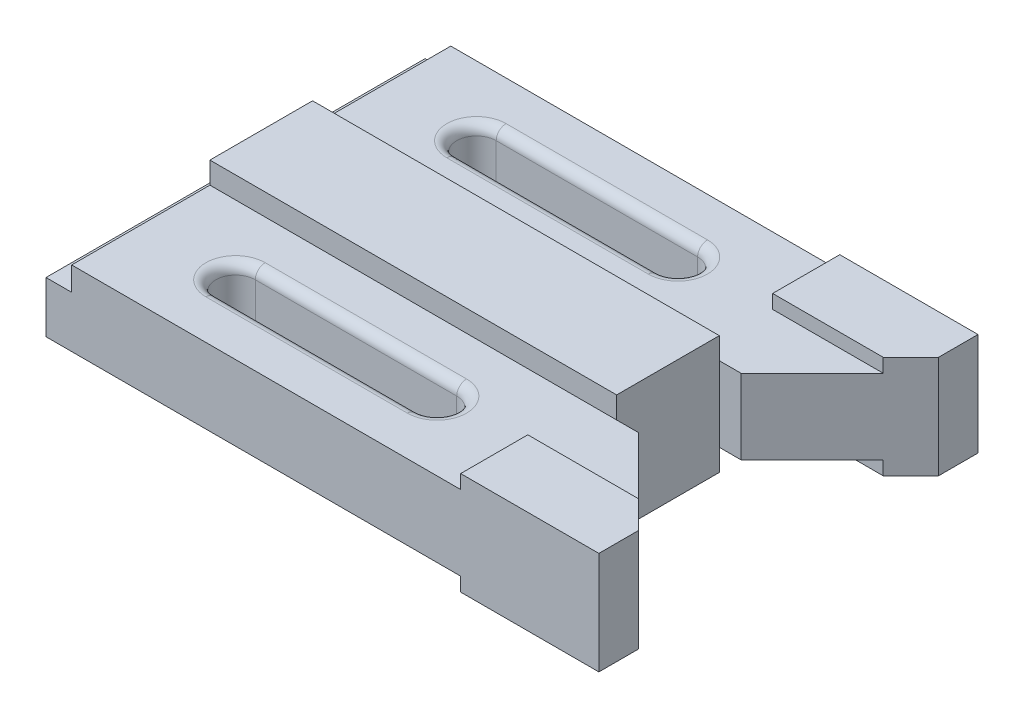
SolidWorks part; units mm, degrees
material "1060 Alloy"
ref_plane "Front Plane" through (0, 0, 0) normal (0, 0, 1) x (1, 0, 0)
ref_plane "Top Plane" through (0, 0, 0) normal (0, 1, 0) x (1, 0, 0)
ref_plane "Right Plane" through (0, 0, 0) normal (1, 0, 0) x (0, 0, -1)
sketch "Sketch1" plane through (0, 0, 0) normal (0, 1, 0) x (1, 0, 0)
  line L0 (0, -48) -> (0, 48)
  line L1 (0, 48) -> (140, 48)
  line L2 (140, 48) -> (140, 38)
  line L3 (140, 38) -> (115, 13)
  line L6 (115, 13) -> (109.5, 13)
  line L7 (109.5, 13) -> (109.5, -13)
  line L8 (109.5, 0) -> (0, 0) construction
  line L9 (105, 48) -> (105, 31)
  line L10 (105, 31) -> (133, 31)
  line L11 (115, 13) -> (0, 13)
  line L12 (0, 30.5) -> (30.5, 30.5)
  line L13 (30.5, 30.5) -> (81.5, 30.5) construction
  line L14 (30.5, 35.5) -> (81.5, 35.5)
  line L15 (30.5, 25.5) -> (81.5, 25.5)
  line L16 (0, -30.5) -> (30.5, -30.5)
  line L17 (115, -13) -> (0, -13)
  line L18 (105, -31) -> (133, -31)
  line L19 (105, -48) -> (105, -31)
  line L20 (115, -13) -> (109.5, -13)
  line L21 (140, -38) -> (115, -13)
  line L22 (140, -48) -> (140, -38)
  line L23 (0, -48) -> (140, -48)
  line L24 (30.5, -30.5) -> (81.5, -30.5) construction
  line L25 (30.5, -35.5) -> (81.5, -35.5)
  line L26 (30.5, -25.5) -> (81.5, -25.5)
  arc A0 (30.5, 35.5) -> (30.5, 25.5) centre (30.5, 30.5) ccw
  arc A1 (81.5, 25.5) -> (81.5, 35.5) centre (81.5, 30.5) ccw
  arc A2 (30.5, -35.5) -> (30.5, -25.5) centre (30.5, -30.5) cw
  arc A3 (81.5, -25.5) -> (81.5, -35.5) centre (81.5, -30.5) cw
  point P14 (15.25, 30.5)
  point P15 (56, 30.5)
  point P33 (56, -30.5)
  dimension "D11" = 5
  dimension "D1" = 48
  dimension "D2" = 140
  dimension "D3" = 10
  dimension "D4" = 17
  dimension "D5" = 35
  dimension "D6" = 45
  dimension "D7" = 30.5
  dimension "D8" = 35
  dimension "D9" = 30.5
  dimension "D10" = 17.5
  dimension "D12" = 51
extrude "Boss-Extrude2" add sketch "Sketch1" along normal mid plane 30 contours L17 L7 L11 L0 region at (54.75, 0, 0)
extrude "Boss-Extrude5" add sketch "Sketch1<6>" along normal mid plane 19 contours A1 L15 A0 L0 L11 L6 L3 L10 L9 L1 L14 | L26 A3 L25 A2 L0 L23 L19 L18 L21 L17 region at (1.3753, 0, 39.25) region at (1.3753, 0, -21.75)
sketch "Sketch1<6>" plane through (0, 0, 0) normal (0, 1, 0) x (1, 0, 0) same geometry as "Sketch1"
extrude "Boss-Extrude6" add sketch "Sketch1<7>" along normal mid plane 26 contours L19 L23 L22 L21 L18 | L9 L10 L3 L2 L1 region at (121.8487, 0, 39.7648) region at (121.8487, 0, -39.7648)
sketch "Sketch1<7>" plane through (0, 0, 0) normal (0, 1, 0) x (1, 0, 0) same geometry as "Sketch1"
sketch "Sketch2" plane through (0, 0, -48) normal (0, 0, -1) x (-1, 0, 0)
  line L1 (0, 15) -> (-6.5, 15)
  line L2 (0, 15) -> (0, 3.5)
  line L3 (0, 3.5) -> (-6.5, 3.5)
  line L4 (-6.5, 15) -> (-6.5, 3.5)
  dimension "D1" = 11.5
  dimension "D2" = 6.5
extrude "Cut-Extrude1" cut sketch "Sketch2" against normal through all
fillet "Fillet1" radius 2.5 16 edges at (56, 9.5, 25.5) (56, -9.5, 25.5) (25.5, 9.5, 30.5) (25.5, -9.5, 30.5) (86.5, 9.5, 30.5) (86.5, -9.5, 30.5) (56, 9.5, 35.5) (56, -9.5, 35.5) (56, 9.5, -25.5) (56, -9.5, -25.5) (86.5, 9.5, -30.5) (86.5, -9.5, -30.5) (25.5, 9.5, -30.5) (25.5, -9.5, -30.5) (56, 9.5, -35.5) (56, -9.5, -35.5)
